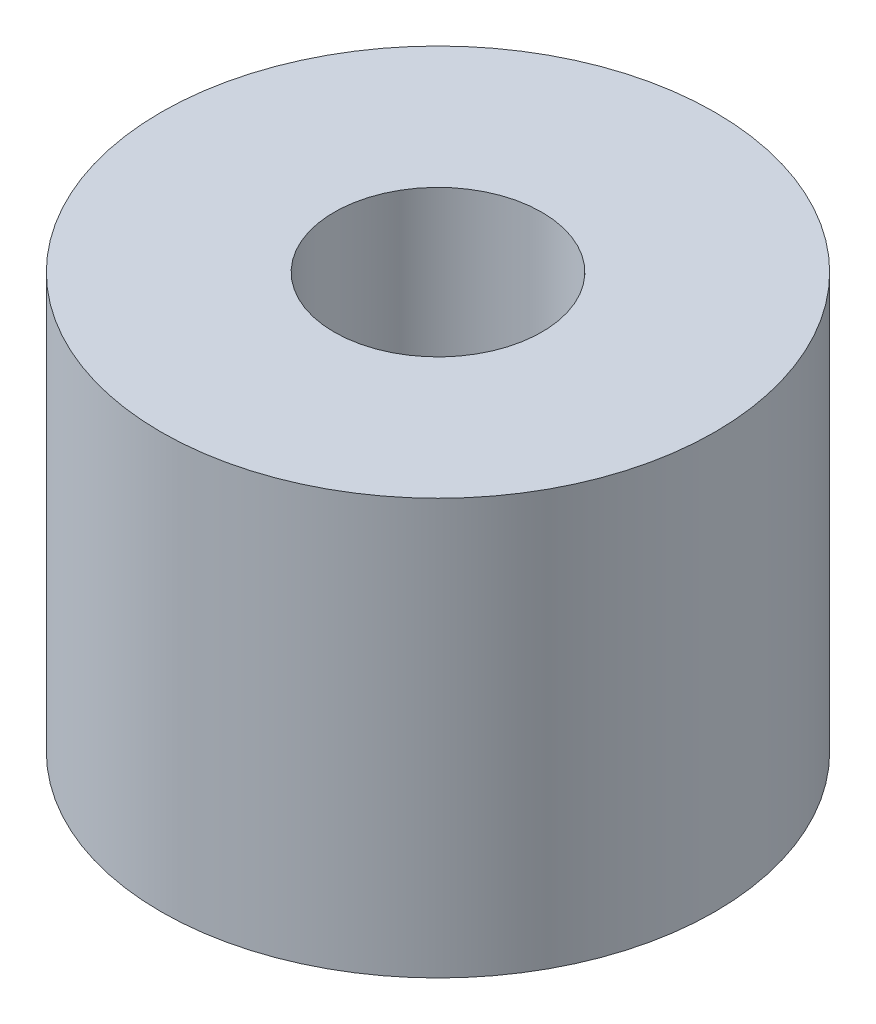
SolidWorks part; units mm, degrees
ref_plane "Front Plane" through (0, 0, 0) normal (0, 0, 1) x (1, 0, 0)
ref_plane "Top Plane" through (0, 0, 0) normal (0, 1, 0) x (1, 0, 0)
ref_plane "Right Plane" through (0, 0, 0) normal (1, 0, 0) x (0, 0, -1)
sketch "Sketch1" plane through (0, 0, 0) normal (0, 1, 0) x (1, 0, 0)
  circle A0 centre (0, 0) radius 4
  circle A1 centre (0, 0) radius 1.5
extrude "Boss-Extrude1" add sketch "Sketch1" along normal blind 6
